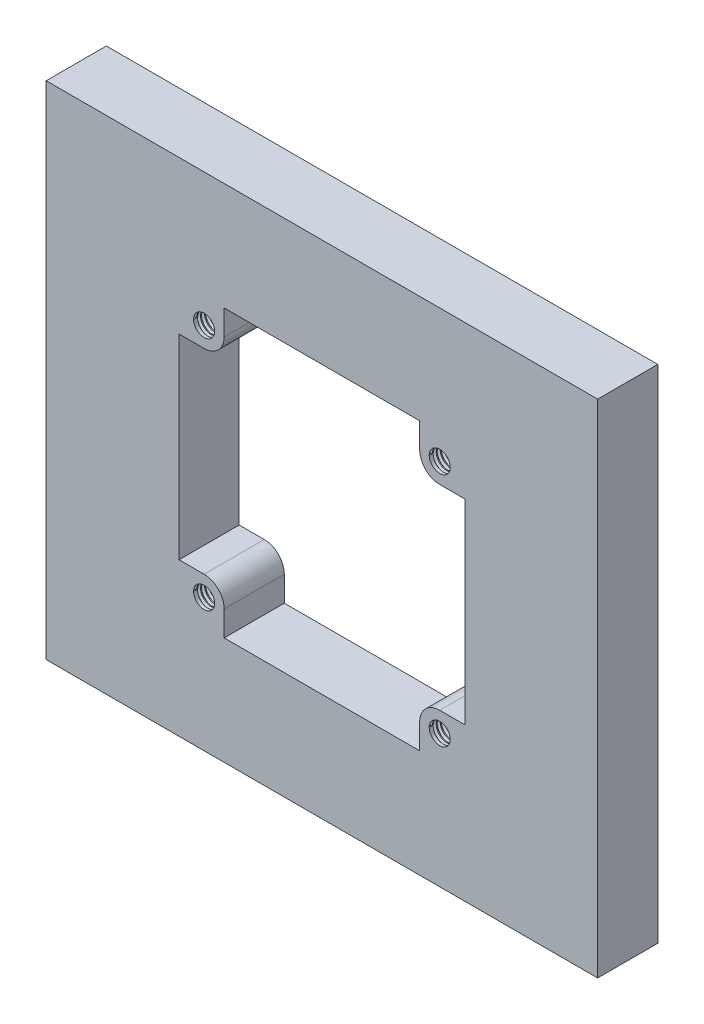
SolidWorks part; units mm, degrees
ref_plane "Ebene vorne" through (0, 0, 0) normal (0, 0, 1) x (1, 0, 0)
ref_plane "Ebene oben" through (0, 0, 0) normal (0, 1, 0) x (1, 0, 0)
ref_plane "Ebene rechts" through (0, 0, 0) normal (1, 0, 0) x (0, 0, -1)
sketch "Skizze1" plane through (0, 0, 0) normal (0, 0, 1) x (1, 0, 0)
  line L0 (0, 0) -> (110, 0)
  line L1 (110, 0) -> (110, 100)
  line L2 (110, 100) -> (0, 100)
  line L3 (0, 100) -> (0, 0)
  dimension "D1" = 110
  dimension "D2" = 100
extrude "Aufsatz-Linear austragen1" add sketch "Skizze1" along normal blind 12
ref_plane "Ebene1" through (55, 0, 0) normal (1, 0, 0) x (0, 0, -1)
ref_plane "Ebene2" through (0, 50, 0) normal (0, 1, 0) x (1, 0, 0)
hole_wizard "M5 Gewindebohrung1" positions "Skizze6" profile "Skizze7" tap size "M5" standard "DIN"
sketch "Skizze6" plane through (0, 0, 0) normal (0, -1, 0) x (-1, 0, 0)
  line L0 (-55, 0) -> (-55, -20.0959) construction
  line L1 (0, 0) -> (-110, 0) construction
  line L3 (-110, -6) -> (3.7683, -6) construction
  line L4 (-110, -12) -> (-110, 0) construction
  point P14 (-95, -6)
  point P16 (-15, -6)
  dimension "D1" = 80
sketch "Skizze7" plane through (15, 0, 6) normal (1, 0, 0) x (0, 0, -1)
  line L0 (0, 0) -> (0, 14)
  line L1 (0, 14) -> (2.1, 12.7382)
  line L2 (2.1, 12.7382) -> (2.1, 0.425)
  line L3 (2.1, 0.425) -> (2.525, 0)
  line L5 (2.525, 0) -> (0, 0)
  line L6 (-2.1, 0.425) -> (-2.525, 0) construction
  line L10 (0, 14) -> (-2.1, 12.7382) construction
  line L11 (0, -6.35) -> (0, 107.95) construction
  dimension "Bohrerdurchmesser" = 4.2
  dimension "Bohrungstiefe" = 14
  dimension "Senkdurchmesser (Oben)" = 5.05
  dimension "Senkwinkel (Oben)" = 90
  dimension "Spitzenwinkel" = 118
cosmetic thread "Bohrungsgewinde1" parameters "D1"=10, "D2"=5
cosmetic thread "Bohrungsgewinde2" parameters "D1"=10, "D2"=5
sketch "Skizze8" plane through (0, 0, 0) normal (0, 0, -1) x (-1, 0, 0)
  line L0 (-55, 101.5707) -> (-55, -13.7402) construction
  line L1 (-115.8696, 50) -> (5.8696, 50) construction
  line L7 (-74.5, 73.5) -> (-74.5, 78.5)
  line L9 (-78.5, 26.5) -> (-31.5, 26.5) construction
  line L10 (-78.5, 26.5) -> (-78.5, 73.5) construction
  line L11 (0, 0) -> (-110, 0) construction
  line L12 (0, 100) -> (0, 0) construction
  line L28 (-78.5, 73.5) -> (-31.5, 73.5) construction
  line L29 (-31.5, 26.5) -> (-31.5, 73.5) construction
  line L30 (-78.5, 26.5) -> (-31.5, 73.5) construction
  line L31 (-75.6716, 70.6716) -> (-31.5, 26.5) construction
  line L32 (-74.5, 21.5) -> (-35.5, 21.5)
  line L33 (-83.5, 30.5) -> (-83.5, 69.5)
  line L34 (-74.5, 78.5) -> (-35.5, 78.5)
  line L35 (-26.5, 30.5) -> (-26.5, 69.5)
  line L36 (-78.5, 26.5) -> (-26.5, 78.5) construction
  line L37 (-75.6716, 70.6716) -> (-31.5, 26.5) construction
  line L38 (-78.5, 69.5) -> (-83.5, 69.5)
  line L39 (-78.5, 30.5) -> (-83.5, 30.5)
  line L40 (-74.5, 26.5) -> (-74.5, 21.5)
  line L41 (-31.5, 30.5) -> (-26.5, 30.5)
  line L42 (-35.5, 26.5) -> (-35.5, 21.5)
  line L43 (-31.5, 69.5) -> (-26.5, 69.5)
  line L44 (-35.5, 73.5) -> (-35.5, 78.5)
  arc A4 (-78.5, 69.5) -> (-74.5, 73.5) centre (-78.5, 73.5) ccw
  arc A5 (-35.5, 73.5) -> (-31.5, 69.5) centre (-31.5, 73.5) ccw
  arc A6 (-31.5, 30.5) -> (-35.5, 26.5) centre (-31.5, 26.5) ccw
  arc A7 (-74.5, 26.5) -> (-78.5, 30.5) centre (-78.5, 26.5) ccw
  point P4 (-55, 50)
  point P5 (-55, 50)
  point P12 (-55, 50)
  point P19 (-55, 50)
  dimension "D1" = 47
  dimension "D2" = 8
  dimension "D3" = 50
  dimension "D4" = 55
  dimension "D5" = 57
  dimension "D6" = 57
extrude "Schnitt-Linear austragen1" cut sketch "Skizze8" against normal through all
hole_wizard "M5 Gewindebohrung3" positions "Skizze11" profile "Skizze12" tap size "M5" standard "ISO" end condition through all
sketch "Skizze11" plane through (0, 0, 0) normal (0, 0, -1) x (-1, 0, 0)
  point P0 (-31.5, 26.5)
  point P3 (-78.5, 26.5)
  point P6 (-78.5, 73.5)
  point P9 (-31.5, 73.5)
sketch "Skizze12" plane through (31.5, 26.5, 0) normal (1, 0, 0) x (0, 1, 0)
  line L0 (0, 0) -> (0, 12)
  line L1 (0, 12) -> (2.1, 12)
  line L2 (2.1, 12) -> (2.1, 0)
  line L5 (2.1, 0) -> (0, 0)
  line L11 (0, -6.35) -> (0, 107.95) construction
  dimension "Bohrerdurchmesser" = 4.2
  dimension "Bohrungstiefe" = 12
cosmetic thread "Bohrungsgewinde3" parameters "D1"=10, "D2"=5
cosmetic thread "Bohrungsgewinde4" parameters "D1"=10, "D2"=5
cosmetic thread "Bohrungsgewinde5" parameters "D1"=10, "D2"=5
cosmetic thread "Bohrungsgewinde6" parameters "D1"=10, "D2"=5
thread "Gewinde2" pitch 0.8 method cut profile "Gewindeprofil2" start angle 0, offset 0, length 12, pitch 0.8, diameter 4.2
ref_plane "Ebene4" through (29.4, 26.5, 12) normal (0, -1, 0) x (-1, 0, 0)
sketch "Gewindeprofil2" plane through (29.4, 26.5, 12) normal (0, -1, 0) x (-1, 0, 0)
  line L0 (0, 0) -> (0, 0.8) construction
  line L1 (0, 0) -> (0.433, 0.25)
  line L2 (0.433, 0.25) -> (0.433, 0.35)
  line L3 (0.433, 0.35) -> (0, 0.6)
  line L4 (0.433, 0.3) -> (0, 0.3) construction
  line L11 (0, 0) -> (0, 0.6)
  point P2 (0, 0)
  dimension "Pitch" = 0.8
  dimension "Profile_Angle" = 60
  dimension "Profile_Land" = 0.1
  dimension "Profile_Height" = 0.433
pattern_linear "Lineares Muster1" count 2 spacing 47 along (0, 1, 0) count 2 spacing 47 along (1, 0, 0) of "Gewinde2"
